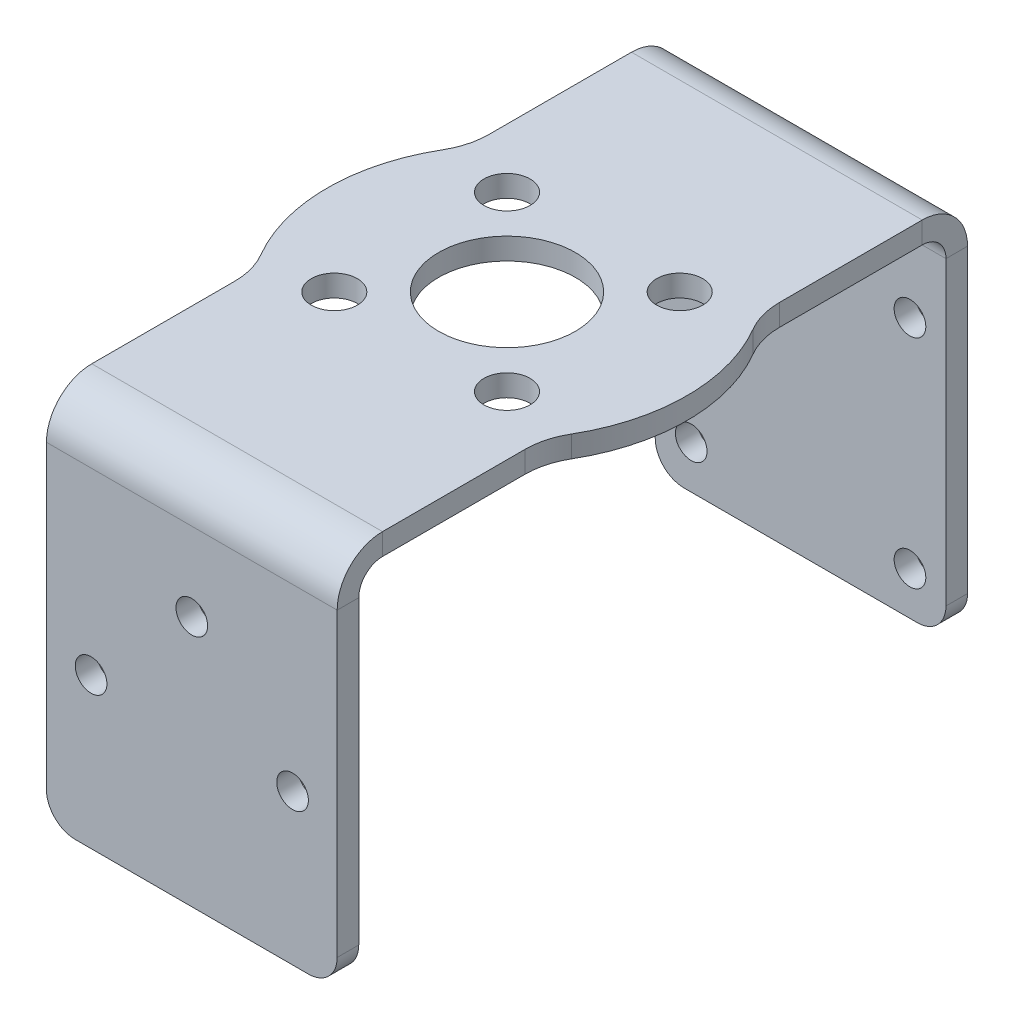
SolidWorks part; units mm, degrees
note: The reader was unsure of these and kept them because the rebuilt part matched: flange length of "Edge-Flange1".
material "1.0037 (S235JR)"
ref_plane "Front Plane" through (0, 0, 0) normal (0, 0, 1) x (1, 0, 0)
ref_plane "Top Plane" through (0, 0, 0) normal (0, 1, 0) x (1, 0, 0)
ref_plane "Right Plane" through (0, 0, 0) normal (1, 0, 0) x (0, 0, -1)
sketch "Sketch1" plane through (0, 0, 0) normal (0, 1, 0) x (1, 0, 0)
  line L1 (10.1, -20.4) -> (-10.1, -20.4)
  line L2 (10.1, -20.4) -> (10.1, 20.4)
  line L3 (10.1, 20.4) -> (-10.1, 20.4)
  line L4 (-10.1, -20.4) -> (-10.1, 20.4)
  line L5 (10.1, -20.4) -> (-10.1, 20.4) construction
  line L6 (10.1, 20.4) -> (-10.1, -20.4) construction
  point P0 (0, 0)
  dimension "D1" = 20.2
  dimension "D2" = 40.8
base flange "Base-Flange1" sketch "Sketch1" thickness 1.5 reverse thickness direction no parameters "D1"=1.65
edge flange "Edge-Flange1" sketch "Sketch10" flange profiles "Sketch10", "Sketch11" flange angle 90 flange length 24.55 flange position material outside bend radius 1.65 thickness 1.5 relief rectangular parameters "D1"=2, "D6"=10, "D8"=1
sketch "Sketch10" plane through (0, -1.5, 20.4) normal (0, 0, 1) x (-1, 0, 0)
  line L0 (10.1, 0) -> (-10.1, 0) construction
  line L1 (10.1, 0) -> (-10.1, 0)
  line L2 (-10.1, 0) -> (-10.1, 24.55)
  line L3 (-10.1, 24.55) -> (10.1, 24.55)
  line L4 (10.1, 24.55) -> (10.1, 0)
sketch "Sketch11" plane through (0, -1.5, -20.4) normal (0, 0, -1) x (1, 0, 0)
  line L0 (10.1, 0) -> (-10.1, 0) construction
  line L1 (10.1, 0) -> (-10.1, 0)
  line L2 (-10.1, 0) -> (-10.1, 24.55)
  line L3 (-10.1, 24.55) -> (10.1, 24.55)
  line L4 (10.1, 24.55) -> (10.1, 0)
bend "EdgeBend1" bend radius 1.65 bend angle 90 parameters "D5"=1
bend "EdgeBend2" bend radius 1.65 bend angle 90 parameters "D5"=2
sketch "Sketch12" plane through (0, 0, -21.9) normal (0, 0, -1) x (-1, 0, 0)
  line L0 (-10.1, -26.05) -> (10.1, -26.05) construction
  line L1 (-7.6, -23.05) -> (7.6, -23.05) construction
  line L2 (-7.6, -23.05) -> (-7.6, -7.95) construction
  line L3 (-7.6, -7.95) -> (7.6, -7.95) construction
  line L4 (7.6, -23.05) -> (7.6, -7.95) construction
  circle A0 centre (-7.6, -7.95) radius 1.1
  circle A1 centre (7.6, -7.95) radius 1.1
  circle A2 centre (7.6, -23.05) radius 1.1
  circle A3 centre (-7.6, -23.05) radius 1.1
  point P4 (0, -7.95)
  dimension "D4" = 2.2
  dimension "D1" = 15.1
  dimension "D2" = 3
  dimension "D3" = 15.2
extrude "Cut-Extrude1" cut sketch "Sketch12" against normal up to next normal cut yes
fillet "Fillet1" radius 2 4 edges at (10.1, -26.05, 21.15) (-10.1, -26.05, 21.15) (-10.1, -26.05, -21.15) (10.1, -26.05, -21.15)
hole_wizard "Ø2.0mm Dowel Hole1" positions "Sketch13" profile "Sketch14" hole size "Ø2.0" standard "ANSI Metric" end condition up to next
sketch "Sketch13" plane through (0, 0, 21.9) normal (0, 0, 1) x (1, 0, 0)
  point P0 (-7, -15.6)
  point P3 (0, -8.6)
  point P6 (7, -15.6)
sketch "Sketch14" plane through (-7, -15.6, 21.9) normal (1, 0, 0) x (0, -1, 0)
  line L0 (0, 0) -> (0, 1.5)
  line L1 (0, 1.5) -> (1.1, 1.5)
  line L2 (1.1, 1.5) -> (1.1, 0)
  line L5 (1.1, 0) -> (0, 0)
  line L11 (0, -6.35) -> (0, 107.95) construction
  dimension "Thru Hole Dia." = 2.2
  dimension "Thru Hole Depth" = 1.5
sketch "Sketch15" plane through (0, 0, 0) normal (0, 1, 0) x (1, 0, 0)
  circle A0 centre (0, 0) radius 12.5
  dimension "D1" = 25
base flange "Tab1" sketch "Sketch15" thickness 1.5 reverse thickness direction no parameters "D1"=1.65
fillet "Fillet2" radius 5 4 edges at (10.1, -0.75, -7.3648) (10.1, -0.75, 7.3648) (-10.1, -0.75, 7.3648) (-10.1, -0.75, -7.3648)
sketch "Sketch18" plane through (0, 0, 0) normal (0, 1, 0) x (1, 0, 0)
  line L1 (6, -6) -> (-6, -6) construction
  line L2 (6, -6) -> (6, 6) construction
  line L3 (6, 6) -> (-6, 6) construction
  line L4 (-6, -6) -> (-6, 6) construction
  line L5 (6, -6) -> (-6, 6) construction
  line L6 (6, 6) -> (-6, -6) construction
  circle A0 centre (-6, 6) radius 1.6
  circle A1 centre (6, 6) radius 1.6
  circle A2 centre (-6, -6) radius 1.6
  circle A3 centre (6, -6) radius 1.6
  circle A4 centre (0, 0) radius 4.75
  point P0 (0, 0)
  dimension "D1" = 3.2
  dimension "D3" = 9.5
  dimension "D2" = 12
extrude "Cut-Extrude2" cut sketch "Sketch18" against normal up to next normal cut yes
sketch "Bend-Lines1" [suppressed] plane through (0, 0, 0) normal (0, 1, 0) x (1, 0, 0)
sketch "Bounding-Box1" [suppressed] plane through (0, 0, 0) normal (0, 1, 0) x (1, 0, 0)
sheet metal parameters "Sheet-Metal1" thickness 1.5 parameters "D1"=2
flat pattern "Flat-Pattern1" [suppressed]
sketch "Bend-Lines2" plane through (0, 0, 0) normal (0, 1, 0) x (1, 0, 0)
sketch3d "Bounding-Box2" [suppressed]
  line L0 (10.1, 20.3, 0) -> (10.1, -20.3, 0) construction
  line L1 (-10.1, 20.3, 0) -> (-10.1, -20.3, 0) construction
  line L2 (10.1, 20.3, 0) -> (-10.1, 20.3, 0) construction
  line L3 (10.1, -20.3, 0) -> (-10.1, -20.3, 0) construction
sheet metal parameters "Sheet-Metal2" thickness 1.5 parameters "D1"=2
flat pattern "Flat-Pattern1"
sketch "Bend-Lines2" plane through (0, 0, 0) normal (0, 1, 0) x (1, 0, 0)
  line L0 (10.1, 20.4598) -> (-10.1, 20.4598) construction
  line L1 (-10.1, -20.4598) -> (10.1, -20.4598) construction
  line L2 (10.1, 20.4598) -> (-10.1, 20.4598) construction
  line L3 (-10.1, -20.4598) -> (10.1, -20.4598) construction
sketch3d "Bounding-Box2" [suppressed]
  line L0 (-10.1, 45.1697, 0) -> (-10.1, -45.1697, 0) construction
  line L1 (10.1, 45.1697, 0) -> (10.1, -45.1697, 0) construction
  line L2 (-10.1, 45.1697, 0) -> (10.1, 45.1697, 0) construction
  line L3 (-10.1, -45.1697, 0) -> (10.1, -45.1697, 0) construction
bend of the flat pattern "EdgeBend1>1"
bend of the flat pattern "EdgeBend2>1"
sheet metal parameters "Sheet-Metal3" thickness 1.5 parameters "D1"=2
flat pattern "Flat-Pattern1"
sketch "Bend-Lines2" plane through (0, 0, 0) normal (0, 1, 0) x (1, 0, 0)
  line L0 (10.1, 20.4598) -> (-10.1, 20.4598) construction
  line L1 (-10.1, -20.4598) -> (10.1, -20.4598) construction
  line L2 (10.1, 20.4598) -> (-10.1, 20.4598) construction
  line L3 (-10.1, -20.4598) -> (10.1, -20.4598) construction
sketch3d "Bounding-Box2" [suppressed]
  line L0 (10.1, 45.1697, 0) -> (10.1, -45.1697, 0) construction
  line L1 (-10.1, 45.1697, 0) -> (-10.1, -45.1697, 0) construction
  line L2 (10.1, 45.1697, 0) -> (-10.1, 45.1697, 0) construction
  line L3 (10.1, -45.1697, 0) -> (-10.1, -45.1697, 0) construction
bend of the flat pattern "EdgeBend1>1"
bend of the flat pattern "EdgeBend2>1"
sheet metal parameters "Sheet-Metal4" thickness 1.5 parameters "D1"=2
flat pattern "Flat-Pattern1"
sketch "Bend-Lines2" plane through (0, 0, 0) normal (0, 1, 0) x (1, 0, 0)
  line L0 (10.1, 20.4598) -> (-10.1, 20.4598) construction
  line L1 (-10.1, -20.4598) -> (10.1, -20.4598) construction
  line L2 (10.1, 20.4598) -> (-10.1, 20.4598) construction
  line L3 (-10.1, -20.4598) -> (10.1, -20.4598) construction
sketch3d "Bounding-Box2" [suppressed]
  line L0 (10.1, 45.1697, 0) -> (10.1, -45.1697, 0) construction
  line L1 (-10.1, 45.1697, 0) -> (-10.1, -45.1697, 0) construction
  line L2 (10.1, 45.1697, 0) -> (-10.1, 45.1697, 0) construction
  line L3 (10.1, -45.1697, 0) -> (-10.1, -45.1697, 0) construction
bend of the flat pattern "EdgeBend1>1"
bend of the flat pattern "EdgeBend2>1"
sheet metal parameters "Sheet-Metal5" thickness 1.5 parameters "D1"=2
flat pattern "Flat-Pattern5"
sketch "Bend-Lines3" plane through (0, 0, 0) normal (0, 1, 0) x (1, 0, 0)
  line L0 (10.1, 20.4598) -> (-10.1, 20.4598) construction
  line L1 (-10.1, -20.4598) -> (10.1, -20.4598) construction
  line L2 (10.1, 20.4598) -> (-10.1, 20.4598) construction
  line L3 (-10.1, -20.4598) -> (10.1, -20.4598) construction
sketch3d "Bounding-Box3" [suppressed]
  line L0 (-12.5, 45.1697, 0) -> (-12.5, -45.1697, 0) construction
  line L1 (12.5, 45.1697, 0) -> (12.5, -45.1697, 0) construction
  line L2 (-12.5, 45.1697, 0) -> (12.5, 45.1697, 0) construction
  line L3 (-12.5, -45.1697, 0) -> (12.5, -45.1697, 0) construction
bend of the flat pattern "EdgeBend2>2"
bend of the flat pattern "EdgeBend1>2"
sheet metal parameters "Sheet-Metal6" thickness 1.5 parameters "D1"=2
flat pattern "Flat-Pattern5"
sketch "Bend-Lines3" plane through (0, 0, 0) normal (0, 1, 0) x (1, 0, 0)
  line L0 (10.1, 20.635) -> (-10.1, 20.635) construction
  line L1 (-10.1, -20.635) -> (10.1, -20.635) construction
  line L2 (10.1, 20.635) -> (-10.1, 20.635) construction
  line L3 (-10.1, -20.635) -> (10.1, -20.635) construction
sketch3d "Bounding-Box3" [suppressed]
  line L0 (-12.5, 45.4199, 0) -> (-12.5, -45.4199, 0) construction
  line L1 (12.5, 45.4199, 0) -> (12.5, -45.4199, 0) construction
  line L2 (-12.5, 45.4199, 0) -> (12.5, 45.4199, 0) construction
  line L3 (-12.5, -45.4199, 0) -> (12.5, -45.4199, 0) construction
bend of the flat pattern "EdgeBend2>2"
bend of the flat pattern "EdgeBend1>2"
